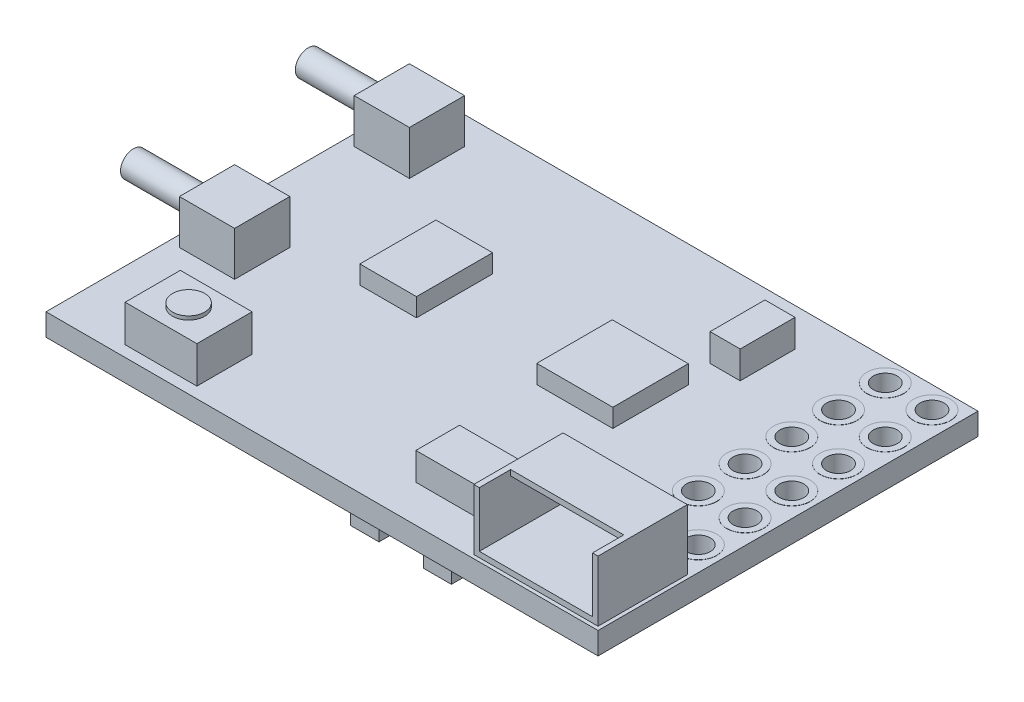
SolidWorks part; units mm, degrees
ref_plane "Front Plane" through (0, 0, 0) normal (0, 0, 1) x (1, 0, 0)
ref_plane "Top Plane" through (0, 0, 0) normal (0, 1, 0) x (1, 0, 0)
ref_plane "Right Plane" through (0, 0, 0) normal (1, 0, 0) x (0, 0, -1)
sketch "Sketch1" plane through (0, 0, 0) normal (0, 1, 0) x (1, 0, 0)
  line L1 (-15, 10.325) -> (15, 10.325)
  line L2 (-15, 10.325) -> (-15, -10.325)
  line L3 (-15, -10.325) -> (15, -10.325)
  line L4 (15, 10.325) -> (15, -10.325)
  line L5 (-15, 10.325) -> (15, -10.325) construction
  line L6 (-15, -10.325) -> (15, 10.325) construction
  point P0 (0, 0)
  dimension "D1" = 30
  dimension "D2" = 20.65
extrude "Boss-Extrude1" add sketch "Sketch1" along normal blind 1.2
sketch "Sketch2" plane through (0, 1.2, 0) normal (0, 1, 0) x (1, 0, 0)
  line L0 (13.7, 10.325) -> (13.7, -10.325) construction
  line L1 (15, 10.325) -> (-15, 10.325) construction
  line L2 (-15, -10.325) -> (15, -10.325) construction
  line L3 (11.16, 9.125) -> (13.7, 9.125) construction
  line L4 (15, -10.325) -> (15, 10.325) construction
  line L5 (13.7, 9.125) -> (13.7, 6.585) construction
  circle A0 centre (13.7, 9.125) radius 0.65
  circle A1 centre (11.16, 9.125) radius 0.65
  circle A2 centre (11.16, 6.585) radius 0.65
  circle A3 centre (11.16, 4.045) radius 0.65
  circle A4 centre (11.16, 1.505) radius 0.65
  circle A5 centre (11.16, -1.035) radius 0.65
  circle A6 centre (11.16, -3.575) radius 0.65
  circle A7 centre (13.7, 6.585) radius 0.65
  circle A8 centre (13.7, 4.045) radius 0.65
  circle A9 centre (13.7, 1.505) radius 0.65
  circle A10 centre (13.7, -1.035) radius 0.65
  circle A11 centre (13.7, -3.575) radius 0.65
  dimension "D3" = 1.3
  dimension "D1" = 1.3
  dimension "D2" = 2
  dimension "D4" = 1.2
  dimension "D6" = 2.54
  dimension "D5" = 6
extrude "Cut-Extrude1" cut sketch "Sketch2" against normal up to next
sketch "Sketch3" plane through (0, 1.2, 0) normal (0, 1, 0) x (1, 0, 0)
  line L0 (-15, -10.325) -> (15, -10.325) construction
  line L1 (14.8, -10.125) -> (8.05, -10.125)
  line L2 (14.8, -10.125) -> (14.8, -5.275)
  line L3 (14.8, -5.275) -> (8.05, -5.275)
  line L4 (8.05, -10.125) -> (8.05, -5.275)
  line L5 (15, -10.325) -> (15, 10.325) construction
  dimension "D1" = 6.75
  dimension "D2" = 4.85
  dimension "D3" = 0.2
  dimension "D4" = 0.2
extrude "Boss-Extrude2" add sketch "Sketch3" along normal blind 3.3
sketch "Sketch4" plane through (0, 1.2, 0) normal (0, 1, 0) x (1, 0, 0)
  line L1 (-14.4, 8.825) -> (-11.4, 8.825)
  line L2 (-14.4, 8.825) -> (-14.4, 5.825)
  line L3 (-14.4, 5.825) -> (-11.4, 5.825)
  line L4 (-11.4, 8.825) -> (-11.4, 5.825)
  line L5 (-15, 10.325) -> (-15, -10.325) construction
  line L6 (-15, 2.575) -> (15, 2.575) construction
  line L7 (15, -10.325) -> (15, 10.325) construction
  line L8 (-14.4, -0.675) -> (-11.4, -0.675)
  line L9 (-11.4, -3.675) -> (-11.4, -0.675)
  line L10 (-14.4, -3.675) -> (-11.4, -3.675)
  line L11 (-14.4, -3.675) -> (-14.4, -0.675)
  line L12 (-14.4, -2.175) -> (-11.4, -2.175) construction
  line L13 (-14.4, 7.325) -> (-11.4, 7.325) construction
  line L14 (15, 10.325) -> (-15, 10.325) construction
  dimension "D1" = 3
  dimension "D2" = 3
  dimension "D3" = 3
  dimension "D4" = 0.6
  dimension "D5" = 9.5
extrude "Boss-Extrude3" add sketch "Sketch4" along normal blind 2.4
sketch "Sketch5" plane through (0, 1.2, 0) normal (0, 1, 0) x (1, 0, 0)
  line L0 (-15, 10.325) -> (-15, -10.325) construction
  line L1 (-11.3, -9.725) -> (-7.4, -9.725)
  line L2 (-11.3, -9.725) -> (-11.3, -6.725)
  line L3 (-11.3, -6.725) -> (-7.4, -6.725)
  line L4 (-7.4, -9.725) -> (-7.4, -6.725)
  line L5 (-15, -10.325) -> (15, -10.325) construction
  dimension "D1" = 3.9
  dimension "D2" = 3
  dimension "D3" = 3.7
  dimension "D4" = 0.6
extrude "Boss-Extrude4" add sketch "Sketch5" along normal blind 2
sketch "Sketch6" plane through (0, 3.2, 0) normal (0, 1, 0) x (1, 0, 0)
  line L0 (-11.3, -8.225) -> (-7.4, -8.225) construction
  line L1 (-11.3, -6.725) -> (-11.3, -9.725) construction
  line L2 (-7.4, -9.725) -> (-7.4, -6.725) construction
  line L3 (-9.35, -6.725) -> (-9.35, -9.725) construction
  line L4 (-7.4, -6.725) -> (-11.3, -6.725) construction
  line L5 (-11.3, -9.725) -> (-7.4, -9.725) construction
  circle A0 centre (-9.35, -8.225) radius 0.875
  dimension "D1" = 1.75
extrude "Boss-Extrude5" add sketch "Sketch6" along normal blind 0.2
sketch "Sketch7" plane through (0, 4.5, 0) normal (0, 1, 0) x (1, 0, 0)
  line L0 (11.425, -5.275) -> (11.425, -10.125) construction
  line L1 (14.8, -5.275) -> (8.05, -5.275) construction
  line L2 (8.05, -10.125) -> (14.8, -10.125) construction
  line L3 (8.05, -10.125) -> (14.8, -10.125) construction
  line L4 (8.35, -10.125) -> (14.5, -10.125)
  line L5 (8.35, -10.125) -> (8.35, -8.425)
  line L6 (8.35, -8.425) -> (14.5, -8.425)
  line L7 (14.5, -10.125) -> (14.5, -8.425)
  line L8 (8.05, -5.275) -> (8.05, -10.125) construction
  point P12 (11.425, -8.425)
  dimension "D1" = 0.3
  dimension "D2" = 1.7
extrude "Cut-Extrude2" cut sketch "Sketch7" against normal offset from surface (3 mm away) 0.3 up to face at (11.16, 1.2, 4.225)
sketch "Sketch8" plane through (0, 0, 8.425) normal (0, 0, 1) x (1, 0, 0)
  line L0 (14.5, 1.5) -> (14.5, 4.5) construction
  line L1 (8.35, 1.5) -> (14.5, 1.5)
  line L2 (8.35, 1.5) -> (8.35, 4.2)
  line L3 (8.35, 4.2) -> (14.5, 4.2)
  line L4 (14.5, 1.5) -> (14.5, 4.2)
  line L5 (14.5, 4.5) -> (8.35, 4.5) construction
  dimension "D1" = 0.3
extrude "Cut-Extrude3" cut sketch "Sketch8" against normal offset from surface (2.85 mm away) 0.3 up to face at (11.425, 2.85, 5.275)
sketch "Sketch9" plane through (0, 1.2, 0) normal (0, 1, 0) x (1, 0, 0)
  line L1 (5.896, 3.685) -> (1.7624, 3.685)
  line L2 (5.896, 3.685) -> (5.896, -0.4166)
  line L3 (5.896, -0.4166) -> (1.7624, -0.4166)
  line L4 (1.7624, 3.685) -> (1.7624, -0.4166)
  line L5 (-7.7224, 3.5888) -> (-4.6463, 3.5888)
  line L6 (-7.7224, 3.5888) -> (-7.7224, -0.5447)
  line L7 (-7.7224, -0.5447) -> (-4.6463, -0.5447)
  line L8 (-4.6463, 3.5888) -> (-4.6463, -0.5447)
extrude "Boss-Extrude6" add sketch "Sketch9" along normal blind 1
sketch "Sketch10" plane through (0, 1.2, 0) normal (0, 1, 0) x (1, 0, 0)
  line L1 (7.1136, 8.2672) -> (5.4794, 8.2672)
  line L2 (7.1136, 8.2672) -> (7.1136, 5.2871)
  line L3 (7.1136, 5.2871) -> (5.4794, 5.2871)
  line L4 (5.4794, 8.2672) -> (5.4794, 5.2871)
  line L5 (7.5302, -5.928) -> (3.0762, -5.928)
  line L6 (7.5302, -5.928) -> (7.5302, -8.2992)
  line L7 (7.5302, -8.2992) -> (3.0762, -8.2992)
  line L8 (3.0762, -5.928) -> (3.0762, -8.2992)
extrude "Boss-Extrude7" add sketch "Sketch10" along normal blind 1.5
sketch "Sketch11" plane through (0, 0, 0) normal (0, -1, 0) x (1, 0, 0)
  line L1 (-6.3538, 2.621) -> (0.4959, 2.621)
  line L2 (-6.3538, 2.621) -> (-6.3538, -4.2287)
  line L3 (-6.3538, -4.2287) -> (0.4959, -4.2287)
  line L4 (0.4959, 2.621) -> (0.4959, -4.2287)
  line L6 (-15, -10.325) -> (-15, 10.325) construction
  line L7 (6.1467, 9.4396) -> (4.628, 9.4396)
  line L8 (6.1467, 9.4396) -> (6.1467, 6.4332)
  line L9 (6.1467, 6.4332) -> (4.628, 6.4332)
  line L10 (4.628, 9.4396) -> (4.628, 6.4332)
  line L11 (2.1795, 9.4086) -> (0.6298, 9.4086)
  line L12 (2.1795, 9.4086) -> (2.1795, 6.3402)
  line L13 (2.1795, 6.3402) -> (0.6298, 6.3402)
  line L14 (0.6298, 9.4086) -> (0.6298, 6.3402)
  line L15 (4.9689, 5.6274) -> (6.1467, 5.6274)
  line L16 (4.9689, 5.6274) -> (4.9689, 2.8689)
  line L17 (4.9689, 2.8689) -> (6.1467, 2.8689)
  line L18 (6.1467, 5.6274) -> (6.1467, 2.8689)
  line L19 (-15, -4.3837) -> (-12.1398, -4.3837)
  line L20 (-15, -4.3837) -> (-15, -8.5679)
  line L21 (-15, -8.5679) -> (-12.1398, -8.5679)
  line L22 (-12.1398, -4.3837) -> (-12.1398, -8.5679)
  line L23 (-13.5965, 3.7987) -> (-11.21, 3.7987)
  line L24 (-13.5965, 3.7987) -> (-13.5965, 0.6993)
  line L25 (-13.5965, 0.6993) -> (-11.21, 0.6993)
  line L26 (-11.21, 3.7987) -> (-11.21, 0.6993)
  line L27 (-10.0012, -6.3053) -> (-8.7304, -6.3053)
  line L28 (-10.0012, -6.3053) -> (-10.0012, -9.4667)
  line L29 (-10.0012, -9.4667) -> (-8.7304, -9.4667)
  line L30 (-8.7304, -6.3053) -> (-8.7304, -9.4667)
extrude "Boss-Extrude8" add sketch "Sketch11" along normal blind 1.5
sketch "Sketch12" plane through (0, 1.2, 0) normal (0, 1, 0) x (1, 0, 0)
  circle A0 centre (11.16, 9.125) radius 1
  circle A1 centre (13.7, 9.125) radius 1
  circle A2 centre (13.7, 6.585) radius 1
  circle A3 centre (11.16, 6.585) radius 1
  circle A4 centre (11.16, 4.045) radius 1
  circle A5 centre (13.7, 4.045) radius 1
  circle A6 centre (13.7, 1.505) radius 1
  circle A7 centre (11.16, 1.505) radius 1
  circle A8 centre (11.16, -1.035) radius 1
  circle A9 centre (11.16, -3.575) radius 1
  circle A10 centre (13.7, -3.575) radius 1
  circle A11 centre (13.7, -1.035) radius 1
  circle A12 centre (11.16, -3.575) radius 0.65 construction
  circle A13 centre (13.7, -3.575) radius 0.65 construction
  circle A14 centre (13.7, -1.035) radius 0.65 construction
  circle A15 centre (11.16, -1.035) radius 0.65 construction
  circle A16 centre (11.16, 1.505) radius 0.65 construction
  circle A17 centre (13.7, 1.505) radius 0.65 construction
  circle A18 centre (13.7, 4.045) radius 0.65 construction
  circle A19 centre (11.16, 4.045) radius 0.65 construction
  circle A20 centre (11.16, 6.585) radius 0.65 construction
  circle A21 centre (13.7, 6.585) radius 0.65 construction
  circle A22 centre (13.7, 9.125) radius 0.65 construction
  circle A23 centre (11.16, 9.125) radius 0.65 construction
  circle A24 centre (11.16, -3.575) radius 0.65
  circle A25 centre (13.7, -3.575) radius 0.65
  circle A26 centre (13.7, -1.035) radius 0.65
  circle A27 centre (11.16, -1.035) radius 0.65
  circle A28 centre (11.16, 1.505) radius 0.65
  circle A29 centre (13.7, 1.505) radius 0.65
  circle A30 centre (13.7, 4.045) radius 0.65
  circle A31 centre (11.16, 4.045) radius 0.65
  circle A32 centre (11.16, 6.585) radius 0.65
  circle A33 centre (13.7, 6.585) radius 0.65
  circle A34 centre (13.7, 9.125) radius 0.65
  circle A35 centre (11.16, 9.125) radius 0.65
  dimension "D1" = 2
extrude "Boss-Extrude9" add sketch "Sketch12" along normal blind 0.01
ref_plane "Plane1" through (0, 0.6, 0) normal (0, 1, 0) x (1, 0, 0)
mirror "Mirror1" about plane through (0, 0.6, 0) normal (0, 1, 0) of "Boss-Extrude9"
sketch "Sketch13" plane through (-14.4, 0, 0) normal (-1, 0, 0) x (0, 0, 1)
  line L0 (-8.825, 1.2) -> (-5.825, 3.6) construction
  line L1 (0.675, 1.2) -> (3.675, 3.6) construction
  circle A0 centre (-7.325, 2.4) radius 0.7
  circle A1 centre (2.175, 2.4) radius 0.7
  dimension "D1" = 1.4
extrude "Boss-Extrude10" add sketch "Sketch13" along normal blind 4
